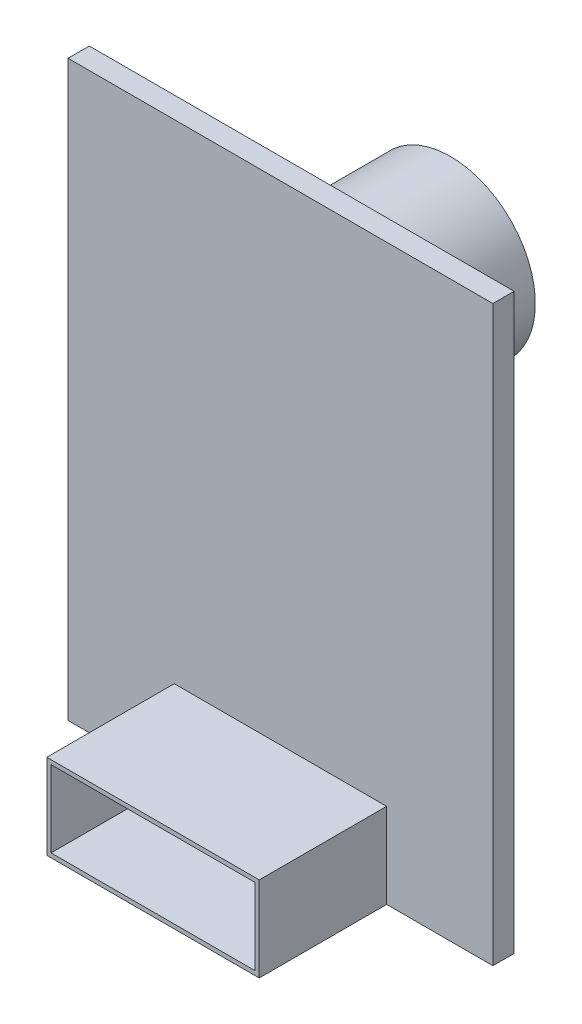
SolidWorks part; units mm, degrees
ref_plane "Front" through (0, 0, 0) normal (0, 0, 1) x (1, 0, 0)
ref_plane "Top" through (0, 0, 0) normal (0, 1, 0) x (1, 0, 0)
ref_plane "Right" through (0, 0, 0) normal (1, 0, 0) x (0, 0, -1)
sketch "Sketch1" plane through (0, 0, 0) normal (0, 0, 1) x (1, 0, 0)
  line L1 (-10, 13.5) -> (10, 13.5)
  line L2 (-10, 13.5) -> (-10, -13.5)
  line L3 (-10, -13.5) -> (10, -13.5)
  line L4 (10, 13.5) -> (10, -13.5)
  line L5 (-10, 13.5) -> (10, -13.5) construction
  line L6 (-10, -13.5) -> (10, 13.5) construction
  point P0 (0, 0)
  dimension "D1" = 20
  dimension "D2" = 27
extrude "Boss-Extrude1" add sketch "Sketch1" along normal blind 1
sketch "Sketch2" plane through (0, 0, 0) normal (0, 0, -1) x (-1, 0, 0)
  line L0 (-10, 13.5) -> (10, 13.5) construction
  line L1 (-4, 10.5) -> (4, 10.5)
  line L2 (-4, 10.5) -> (-4, 2.5)
  line L3 (-4, 2.5) -> (4, 2.5)
  line L4 (4, 10.5) -> (4, 2.5)
  line L5 (-4, 10.5) -> (4, 2.5) construction
  line L6 (-4, 2.5) -> (4, 10.5) construction
  line L7 (0, 6.5) -> (0, 0) construction
  circle A0 centre (0, 6.5) radius 4
  dimension "D1" = 8
  dimension "D2" = 7
extrude "Boss-Extrude2" add sketch "Sketch2" along normal blind 2 contours L1 L4 L3 L2
extrude "Boss-Extrude3" add sketch "Sketch2<3>" along normal blind 7 contours A0
sketch "Sketch2<3>" plane through (0, 0, 0) normal (0, 0, -1) x (-1, 0, 0) same geometry as "Sketch2"
sketch "Sketch3" plane through (0, 0, 1) normal (0, 0, 1) x (1, 0, 0)
  line L0 (-10, -13.5) -> (10, -13.5) construction
  line L1 (-5, -9.5) -> (5, -9.5)
  line L2 (-5, -9.5) -> (-5, -13.5)
  line L3 (-5, -13.5) -> (5, -13.5)
  line L4 (5, -9.5) -> (5, -13.5)
  line L5 (-5, -9.5) -> (5, -13.5) construction
  line L6 (-5, -13.5) -> (5, -9.5) construction
  line L7 (0, 0) -> (0, -11.5) construction
  point P0 (0, -11.5)
  dimension "D1" = 4
  dimension "D2" = 10
extrude "Extrude-Thin1" add sketch "Sketch3" along normal blind 6 thin thin type one direction reverse wall 0.2
